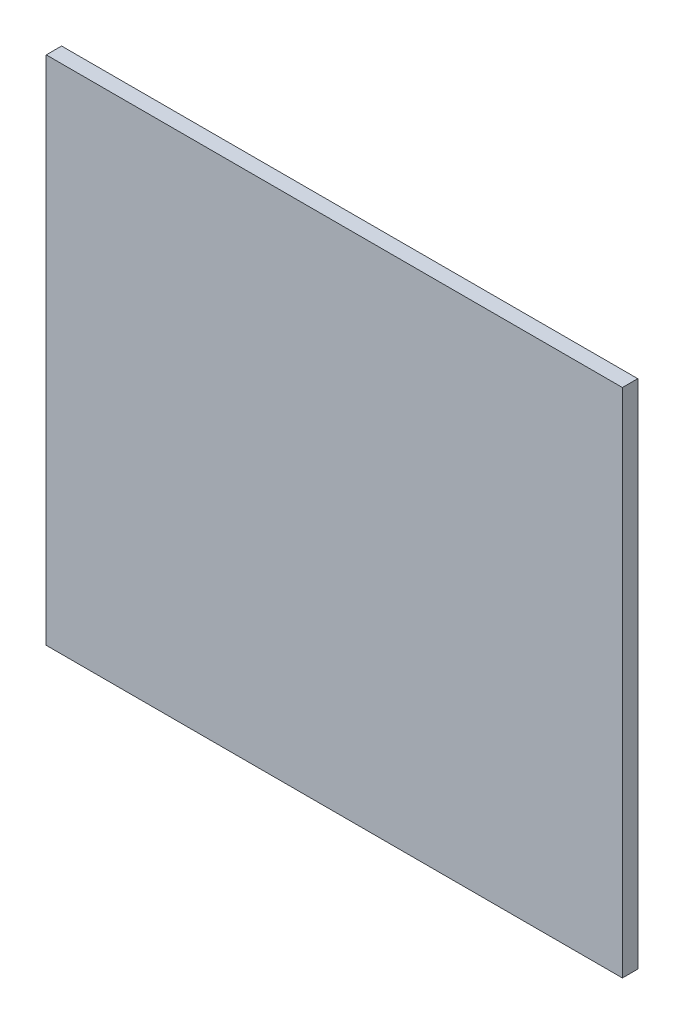
SolidWorks part; units mm, degrees
ref_plane "Front Plane" through (0, 0, 0) normal (0, 0, 1) x (1, 0, 0)
ref_plane "Top Plane" through (0, 0, 0) normal (0, 1, 0) x (1, 0, 0)
ref_plane "Right Plane" through (0, 0, 0) normal (1, 0, 0) x (0, 0, -1)
sketch "Sketch1" plane through (0, 0, 0) normal (0, 0, 1) x (1, 0, 0)
  line L1 (-169, -150) -> (169, -150)
  line L2 (-169, -150) -> (-169, 150)
  line L3 (-169, 150) -> (169, 150)
  line L4 (169, -150) -> (169, 150)
  line L5 (-169, -150) -> (169, 150) construction
  line L6 (-169, 150) -> (169, -150) construction
  point P0 (0, 0)
  dimension "D1" = 338
  dimension "D2" = 300
extrude "Boss-Extrude1" add sketch "Sketch1" along normal blind 9
equation "\"PCWidth\"= 172mm"
equation "\"PCLength\"= 320mm"
equation "\"PCHeight\"= 242mm"
equation "\"WallThickness\"= 9mm"
equation "\"ThermoBarrierThickness\"= 3mm"
equation "\"HotSideGap\"= 50mm"
equation "\"PCClearance\"= 25mm"
equation "\"D1@Sketch1\"=\"PCLength\" + (2 * \"WallThickness\")"
equation "\"D2@Sketch1\"=\"RadiatorHeight\" + \"PCClearance\""
equation "\"D1@Boss-Extrude1\"=\"WallThickness\""
equation "\"RadiatorHeight\"= 275mm"
